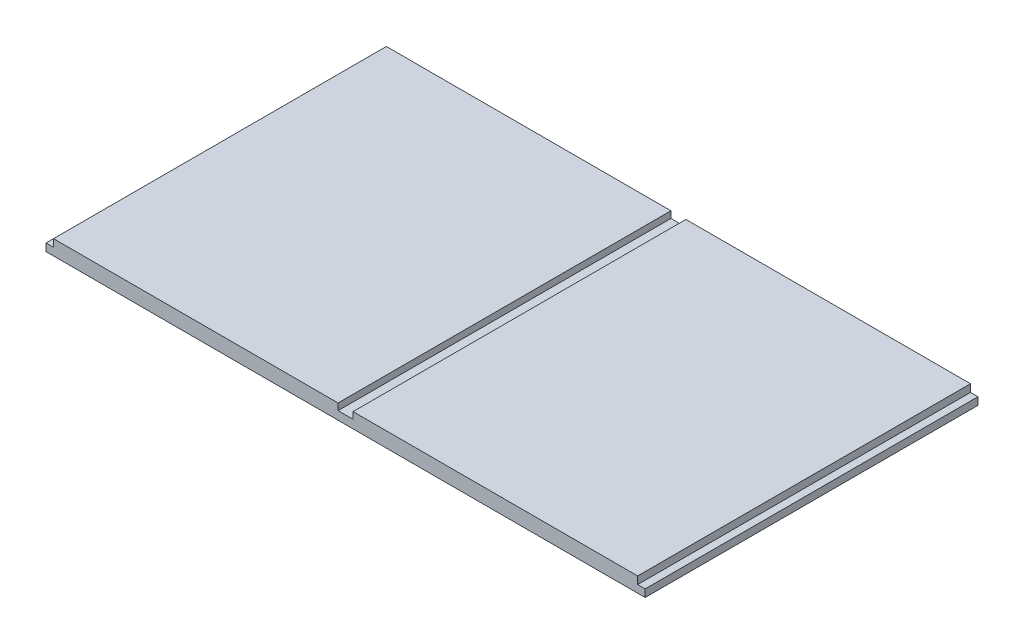
SolidWorks part; units mm, degrees
ref_plane "Front" through (0, 0, 0) normal (0, 0, 1) x (1, 0, 0)
ref_plane "Top" through (0, 0, 0) normal (0, 1, 0) x (1, 0, 0)
ref_plane "Right" through (0, 0, 0) normal (1, 0, 0) x (0, 0, -1)
sketch "Sketch1" plane through (0, 0, 0) normal (0, 1, 0) x (1, 0, 0)
  line L1 (-360, -200) -> (360, -200)
  line L2 (-360, -200) -> (-360, 200)
  line L3 (-360, 200) -> (360, 200)
  line L4 (360, -200) -> (360, 200)
  line L5 (-360, -200) -> (360, 200) construction
  line L6 (-360, 200) -> (360, -200) construction
  point P0 (0, 0)
  dimension "D1" = 720
  dimension "D2" = 400
extrude "Boss-Extrude1" add sketch "Sketch1" along normal blind 18
sketch "Sketch2" plane through (0, 18, 0) normal (0, 1, 0) x (1, 0, 0)
  line L0 (360, 200) -> (-360, 200) construction
  line L1 (360, -200) -> (351, -200)
  line L2 (360, -200) -> (360, 200)
  line L3 (360, 200) -> (351, 200)
  line L4 (351, -200) -> (351, 200)
  line L6 (-360, -200) -> (-351, -200)
  line L7 (-360, -200) -> (-360, 200)
  line L8 (-360, 200) -> (-351, 200)
  line L9 (-351, -200) -> (-351, 200)
  dimension "D1" = 9
  dimension "D2" = 9
extrude "Cut-Extrude1" cut sketch "Sketch2" against normal blind 9
sketch "Sketch3" plane through (0, 18, 0) normal (0, 1, 0) x (1, 0, 0)
  line L0 (351, 200) -> (-351, 200) construction
  line L1 (-9, -200) -> (9, -200)
  line L2 (-9, -200) -> (-9, 200)
  line L3 (-9, 200) -> (9, 200)
  line L4 (9, -200) -> (9, 200)
  line L5 (-9, -200) -> (9, 200) construction
  line L6 (-9, 200) -> (9, -200) construction
  point P0 (0, 0)
  dimension "D1" = 18
extrude "Cut-Extrude2" cut sketch "Sketch3" against normal blind 8
